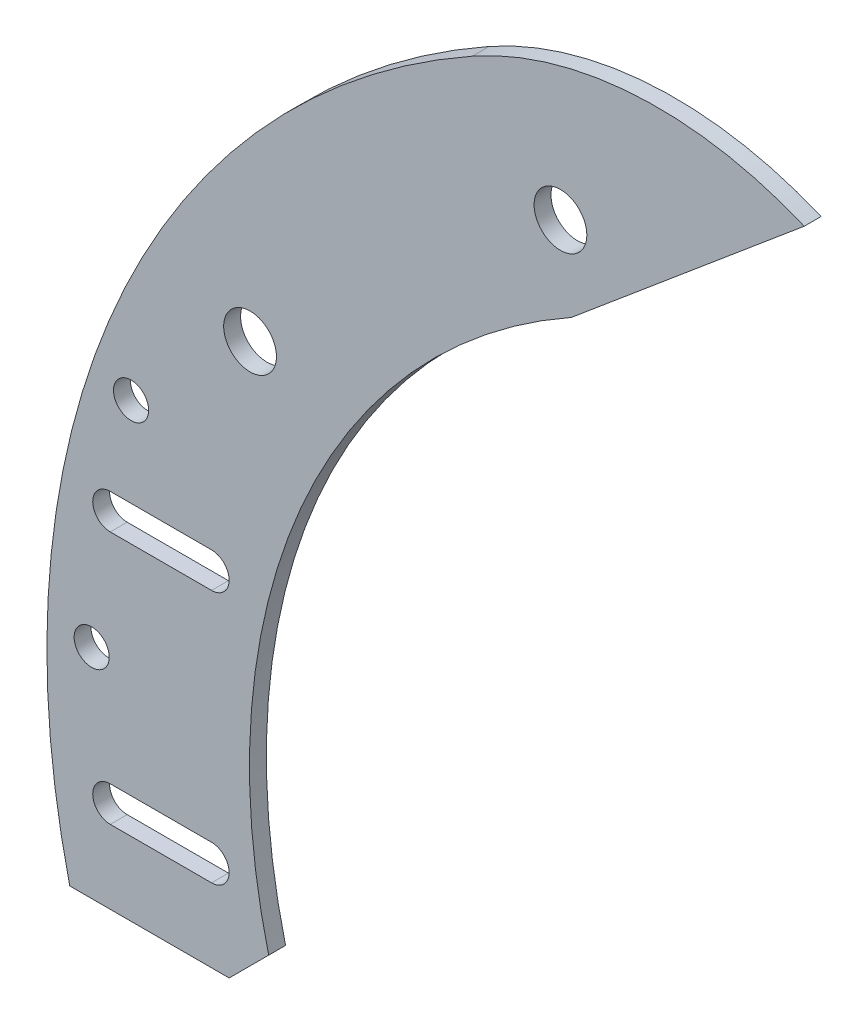
SolidWorks part; units mm, degrees
ref_plane "Front Plane" through (0, 0, 0) normal (0, 0, 1) x (1, 0, 0)
ref_plane "Top Plane" through (0, 0, 0) normal (0, 1, 0) x (1, 0, 0)
ref_plane "Right Plane" through (0, 0, 0) normal (1, 0, 0) x (0, 0, -1)
sketch "Sketch1" plane through (0, 0, 0) normal (0, 0, 1) x (1, 0, 0)
  line L0 (0, -36.5125) -> (-213.3981, -36.5125) construction
  line L1 (-153.9562, -36.5125) -> (-123.979, -36.5125)
  line L2 (-59.6137, 103.2539) -> (-15.8343, 139.9892)
  line L3 (-116.5487, -29.0823) -> (-123.979, -36.5125)
  circle A0 centre (0, 0) radius 36.5125 construction
  arc A5 (-59.6137, 103.2539) -> (-116.5487, -29.0823) centre (-1.7338, -0.0635) ccw
  arc A6 (-78.2349, 136.4933) -> (-153.9562, -36.5125) centre (-1.7338, -0.0635) ccw
  arc A8 (-78.2349, 136.4933) -> (-15.8343, 139.9892) centre (-43.459, 74.4172) cw
  dimension "D1" = 73.025
  dimension "D3" = 1.7338
  dimension "D4" = 118.4253
  dimension "D5" = 38.1
  dimension "D6" = 71.1534
  dimension "D2" = 0.0635
  dimension "D7" = 57.15
  dimension "D8" = 41.7252
  dimension "D9" = 140
  dimension "D10" = 45
  dimension "D11" = 7.4302
extrude "Boss-Extrude1" add sketch "Sketch1" along normal blind 3.175
ref_axis "Axis1" through (0, 0, 0) along (0, 0, 1)
sketch "Sketch2" plane through (0, 0, 3.175) normal (0, 0, 1) x (1, 0, 0)
  line L0 (-146.3362, -19.3675) -> (-127.2862, -19.3675) construction
  line L1 (-146.3362, -16.0655) -> (-127.2862, -16.0655)
  line L2 (-146.3362, -22.6695) -> (-127.2862, -22.6695)
  line L3 (-153.9562, -36.5125) -> (-123.979, -36.5125) construction
  line L5 (-146.3362, 28.2575) -> (-127.2862, 28.2575) construction
  line L6 (-146.3362, 31.5595) -> (-127.2862, 31.5595)
  line L7 (-146.3362, 24.9555) -> (-127.2862, 24.9555)
  arc A0 (-146.3362, -16.0655) -> (-146.3362, -22.6695) centre (-146.3362, -19.3675) ccw
  arc A1 (-127.2862, -22.6695) -> (-127.2862, -16.0655) centre (-127.2862, -19.3675) ccw
  arc A2 (-146.3362, 31.5595) -> (-146.3362, 24.9555) centre (-146.3362, 28.2575) ccw
  arc A3 (-127.2862, 24.9555) -> (-127.2862, 31.5595) centre (-127.2862, 28.2575) ccw
  point P2 (-136.8112, -19.3675)
  point P14 (-136.8112, 28.2575)
  dimension "D3" = 19.05
  dimension "D1" = 6.604
  dimension "D2" = 17.145
  dimension "D4" = 17.145
  dimension "D5" = 6.604
  dimension "D6" = 19.05
  dimension "D7" = 47.625
extrude "Cut-Extrude1" cut sketch "Sketch2" against normal up to surface (3.175 mm away) contours L7 A3 L6 A2 | L1 A1 L2 A0 up to face at (-100.0065, 51.2011, 0)
sketch "Sketch4" plane through (0, 0, 3.175) normal (0, 0, 1) x (1, 0, 0)
  line L0 (-153.9562, -36.5125) -> (-123.979, -36.5125) construction
  line L1 (-135.813, -36.5125) -> (-153.9562, -36.5125) construction
  line L2 (1.3579, 3.5895) -> (-1.7338, -0.0635) construction
  line L3 (-136.8112, 24.9555) -> (-136.8112, -16.0655) construction
  line L4 (-146.3362, 24.9555) -> (-127.2862, 24.9555) construction
  line L5 (-146.3362, -16.0655) -> (-127.2862, -16.0655) construction
  circle A0 centre (-149.8374, 4.445) radius 3.302
  circle A1 centre (-142.4272, 48.3479) radius 3.302
  arc A2 (-136.5058, -34.0622) -> (-135.813, -36.5125) centre (1.3579, 3.5895) ccw construction
  arc A3 (-72.6557, 125.8435) -> (-136.5058, -34.0622) centre (1.3579, 3.5895) ccw construction
  arc A4 (-144.8846, -36.5125) -> (-149.7418, 7.7456) centre (-0.188, 1.763) cw construction
  arc A5 (-78.2349, 136.4933) -> (-153.9562, -36.5125) centre (-1.7338, -0.0635) ccw construction
  arc A6 (-78.2349, 136.4933) -> (-153.9562, -36.5125) centre (-1.7338, -0.0635) ccw construction
  arc A7 (-72.6557, 125.8435) -> (-136.5058, -34.0622) centre (1.3579, 3.5895) ccw construction
  arc A8 (-149.7418, 7.7456) -> (-141.3649, 51.4743) centre (-0.188, 1.763) cw construction
  point P7 (-136.8112, 4.445)
  point P12 (-0.188, 1.763)
  dimension "D1" = 6.604
extrude "Cut-Extrude2" cut sketch "Sketch4" against normal up to surface (3.175 mm away) up to face at (-136.8112, -19.3675, 0)
hole_wizard "25/64 (0.39063) Diameter Hole1" positions "Sketch5" profile "Sketch6" hole size "25/64" standard "ANSI Inch" end condition through all
sketch "Sketch5" plane through (0, 0, 3.175) normal (0, 0, 1) x (1, 0, 0)
  line L0 (-120.0496, 69.1208) -> (-61.677, 118.1012) construction
  line L2 (-59.6137, 103.2539) -> (-15.8343, 139.9892) construction
  point P0 (-120.0496, 69.1208)
  point P2 (-61.677, 118.1012)
  dimension "D1" = 12.7
  dimension "D2" = 50.8
  dimension "D3" = 76.2
sketch "Sketch6" plane through (-120.0496, 69.1208, 3.175) normal (1, 0, 0) x (0, -1, 0)
  line L0 (0, 0) -> (0, 3.175)
  line L1 (0, 3.175) -> (4.961, 3.175)
  line L2 (4.961, 3.175) -> (4.961, 0)
  line L5 (4.961, 0) -> (0, 0)
  line L11 (0, -6.35) -> (0, 107.95) construction
  dimension "Thru Hole Dia." = 9.922
  dimension "Thru Hole Depth" = 3.175
